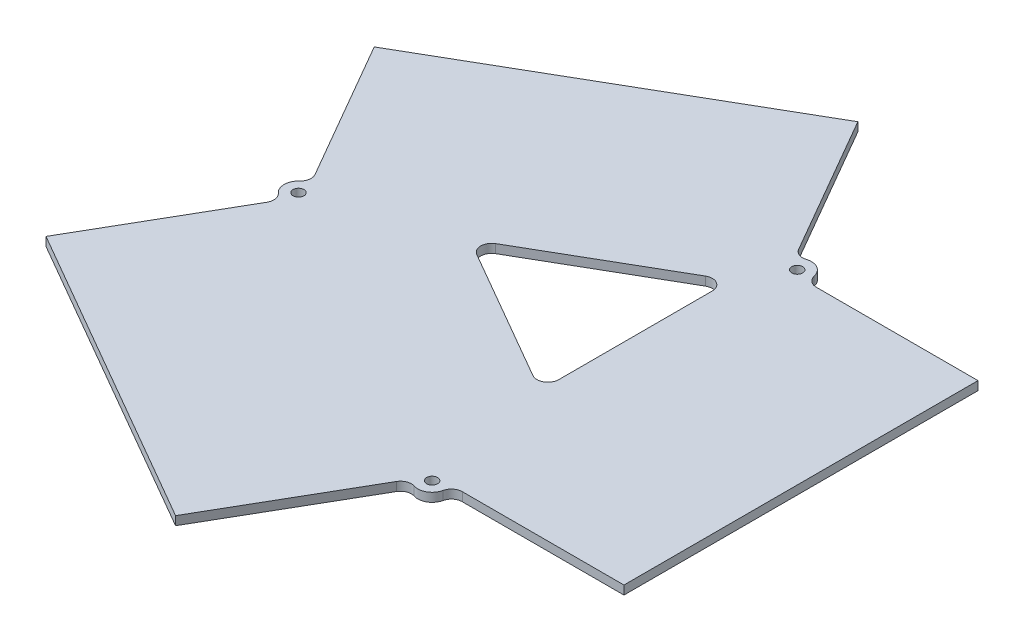
SolidWorks part; units mm, degrees
material "Acrylic (Medium-high impact)"
ref_plane "Front Plane" through (0, 0, 0) normal (0, 0, 1) x (1, 0, 0)
ref_plane "Top Plane" through (0, 0, 0) normal (0, 1, 0) x (1, 0, 0)
ref_plane "Right Plane" through (0, 0, 0) normal (1, 0, 0) x (0, 0, -1)
sketch "Sketch1" plane through (0, 0, 0) normal (0, 1, 0) x (1, 0, 0)
  line L0 (-75.8086, 34.2002) -> (-96.121, 69.3822)
  line L1 (-98.853, 70.1143) -> (-28.705, 110.6143)
  line L2 (-28.705, 110.6143) -> (-8.8981, 76.3079)
  line L4 (-3.2845, 73.0668) -> (36.3291, 73.0668)
  line L5 (36.3291, 73.0668) -> (36.3291, -7.9332)
  line L6 (36.3291, -7.9332) -> (-3.2845, -7.9332)
  line L8 (-8.8981, -11.1742) -> (-28.705, -45.4806)
  line L9 (-28.705, -45.4806) -> (-98.853, -4.9806)
  line L10 (-98.853, -4.9806) -> (-79.0462, 29.3258)
  line L12 (-79.0462, 35.8079) -> (-98.853, 70.1143)
  line L13 (-96.121, 69.3822) -> (-29.437, 107.8822)
  line L14 (-29.437, 107.8822) -> (-9.1246, 72.7002)
  line L15 (-6.2956, 71.0668) -> (34.3291, 71.0668)
  line L16 (34.3291, 71.0668) -> (34.3291, -5.9332)
  line L17 (34.3291, -5.9332) -> (-6.2956, -5.9332)
  line L18 (-9.1246, -7.5665) -> (-29.437, -42.7485)
  line L19 (-29.437, -42.7485) -> (-96.121, -4.2485)
  line L20 (-96.121, -4.2485) -> (-75.8086, 30.9335)
  line L21 (-53.7368, 42.8724) -> (-9.8212, 17.5177)
  line L22 (-6.2956, 74.3335) -> (-9.8212, 68.2271)
  line L23 (-11.8212, 64.763) -> (-49.7368, 42.8724)
  line L24 (-49.7368, 42.8724) -> (-11.8212, 20.9818)
  line L25 (-9.8212, 17.5177) -> (-9.8212, 68.2271)
  line L26 (-11.8212, 20.9818) -> (-11.8212, 64.763)
  line L27 (-9.8212, 68.2271) -> (-53.7368, 42.8724)
  circle A0 centre (-78.6376, 32.5668) radius 1.25
  circle A1 centre (-6.2956, 74.3335) radius 1.25
  circle A2 centre (-6.2956, -9.1998) radius 1.25
  arc A3 (-75.8086, 30.9335) -> (-75.8086, 34.2002) centre (-78.6376, 32.5668) ccw
  arc A4 (-3.2845, 73.0668) -> (-8.8981, 76.3079) centre (-6.2956, 74.3335) ccw
  arc A5 (-6.2956, -5.9332) -> (-9.1246, -7.5665) centre (-6.2956, -9.1998) ccw
  arc A6 (-8.8981, -11.1742) -> (-3.2845, -7.9332) centre (-6.2956, -9.1998) ccw
  arc A7 (-79.0462, 35.8079) -> (-79.0462, 29.3258) centre (-78.6376, 32.5668) ccw
  arc A8 (-9.1246, 72.7002) -> (-6.2956, 71.0668) centre (-6.2956, 74.3335) ccw
  dimension "D1" = 2
extrude "Boss-Extrude1" add sketch "Sketch1" along normal blind 2 contours L12 A7 L10 L9 L8 A6 L6 L5 L4 A4 L2 L1 A0 A2 L14 A8 A1 L15 L16 L17 A5 L18 L19 L20 A3 L0 L13 | A8 L14 L13 L0 A3 L20 L19 L18 A5 L17 L16 L15 L25 L21 L27 | L25 L27 L21 L26 L24 L23 region at (-10.492, 0, -42.8724) region at (-84.2391, 0, -52.7875) region at (-63.6757, 0, -90.1854)
fillet "Fillet1" radius 2.5 9 edges at (-8.8981, 1, -76.3079) (-3.2845, 1, -73.0668) (-8.8981, 1, 11.1742) (-3.2845, 1, 7.9332) (-79.0462, 1, -29.3258) (-79.0462, 1, -35.8079) (-11.8212, 1, -20.9818) (-49.7368, 1, -42.8724) (-11.8212, 1, -64.763)
